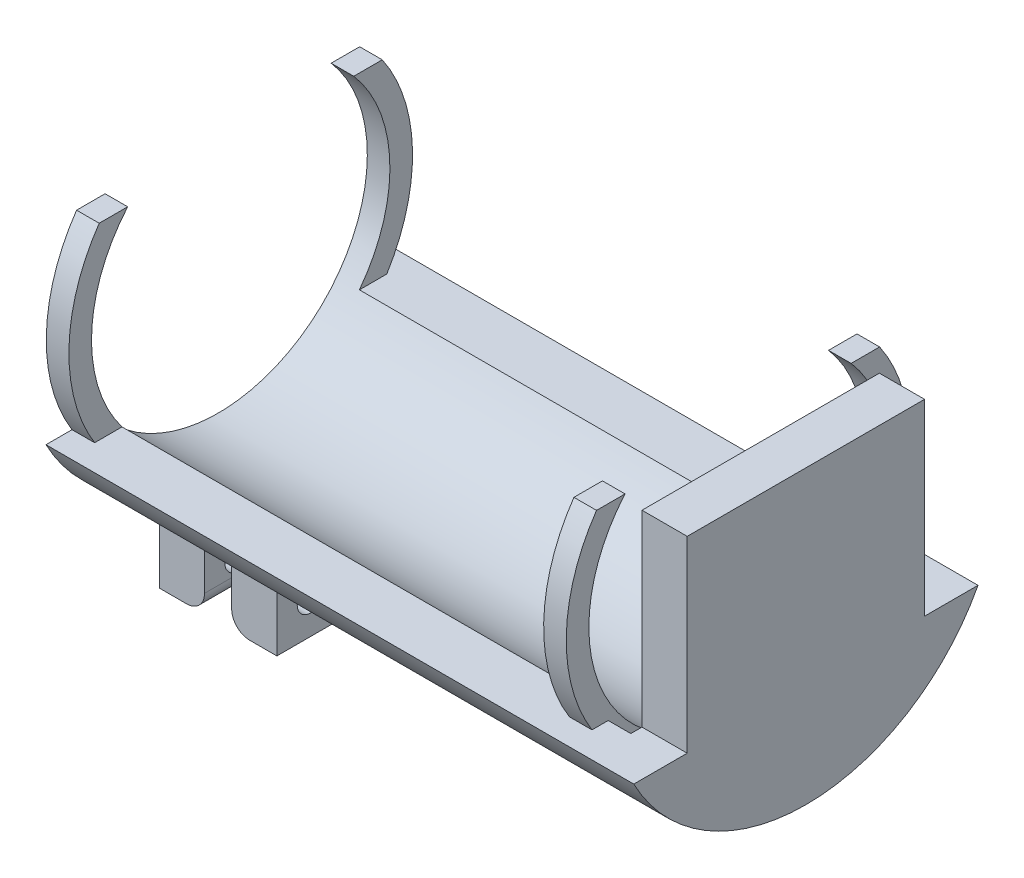
SolidWorks part; units mm, degrees
ref_plane "Front" through (0, 0, 0) normal (0, 0, 1) x (1, 0, 0)
ref_plane "Top" through (0, 0, 0) normal (0, 1, 0) x (1, 0, 0)
ref_plane "Right" through (0, 0, 0) normal (1, 0, 0) x (0, 0, -1)
sketch "Sketch1" plane through (0, 0, 0) normal (1, 0, 0) x (0, 0, -1)
  line L1 (-38.0657, -20) -> (-26.2488, -20)
  line L2 (26.2488, -20) -> (38.0657, -20)
  arc A0 (-26.2488, -20) -> (26.2488, -20) centre (0, 0) ccw
  arc A1 (-38.0657, -20) -> (38.0657, -20) centre (0, 0) ccw
  point P7 (-27.8818, -17.662)
  point P8 (27.8212, -17.6523)
  dimension "D1" = 66
  dimension "D2" = 10
  dimension "D3" = 20
extrude "Boss-Extrude1" add sketch "Sketch1" along normal mid plane 120
sketch "Sketch2" plane through (60, 0, 0) normal (1, 0, 0) x (0, 0, -1)
  line L0 (-31.305, 21.5407) -> (-25, 21.5407)
  line L1 (25, 21.5407) -> (31.305, 21.5407)
  arc A0 (-25, 21.5407) -> (25, 21.5407) centre (0, 0) ccw
  arc A1 (-31.305, 21.5407) -> (31.305, 21.5407) centre (0, 0) ccw
  dimension "D1" = 5
  dimension "D2" = 50
extrude "Boss-Extrude2" add sketch "Sketch2" against normal blind 5 from offset 5 offset against normal yes
sketch "Sketch3" plane through (60, 0, 0) normal (1, 0, 0) x (0, 0, -1)
  line L0 (-26.2488, -20) -> (-26.2488, 21.5407)
  line L1 (-26.2488, 21.5407) -> (26.2488, 21.5407)
  line L2 (26.2488, 21.5407) -> (26.2488, -20)
  line L3 (-25, 21.5407) -> (-31.305, 21.5407) construction
  line L4 (38.0657, -20) -> (26.2488, -20)
  line L7 (-26.2488, -20) -> (-38.0657, -20)
  line L8 (38.0657, -20) -> (26.2488, -20)
  line L11 (-26.2488, -20) -> (-38.0657, -20)
  arc A5 (-26.2488, -20) -> (26.2488, -20) centre (0, 0) ccw
  arc A7 (-38.0657, -20) -> (38.0657, -20) centre (0, 0) ccw
  arc A11 (-38.0657, -20) -> (38.0657, -20) centre (0, 0) ccw
  dimension "D1" = 0
extrude "Boss-Extrude3" add sketch "Sketch3" along normal blind 10
sketch "Sketch4" plane through (0, 0, 0) normal (0, 0, 1) x (1, 0, 0)
  line L0 (-48, -43) -> (-48, -54)
  line L1 (-60, -43) -> (70, -43) construction
  line L2 (-52, -58) -> (-58, -58)
  line L3 (-58, -58) -> (-58, -43)
  line L4 (-45, -43) -> (-45, -58) construction
  line L5 (-58, -43) -> (-48, -43)
  line L6 (-60, -20) -> (-60, -43) construction
  line L7 (-32, -43) -> (-42, -43)
  line L8 (-32, -58) -> (-32, -43)
  line L9 (-38, -58) -> (-32, -58)
  line L10 (-42, -43) -> (-42, -54)
  arc A0 (-38, -58) -> (-42, -54) centre (-38, -54) cw
  arc A1 (-48, -54) -> (-52, -58) centre (-52, -54) cw
  point P16 (-42, -58)
  point P19 (-48, -58)
  dimension "D5" = 4
  dimension "D1" = 15
  dimension "D2" = 3
  dimension "D3" = 10
  dimension "D4" = 15
extrude "Boss-Extrude4" add sketch "Sketch4" along normal mid plane 30 separate body
sketch "Sketch5" plane through (0, -43, 0) normal (0, 1, 0) x (1, 0, 0)
  line L0 (-32, 15) -> (-42, 15) construction
  line L1 (-42, 15) -> (-42, -15) construction
  line L2 (-42, -15) -> (-32, -15) construction
  line L3 (-32, -15) -> (-32, 15) construction
  line L4 (-48, 15) -> (-58, 15) construction
  line L5 (-58, 15) -> (-58, -15) construction
  line L6 (-58, -15) -> (-48, -15) construction
  line L7 (-48, -15) -> (-48, 15) construction
  line L8 (-32, 15) -> (-42, 15)
  line L9 (-42, 15) -> (-42, -15)
  line L10 (-42, -15) -> (-32, -15)
  line L11 (-32, -15) -> (-32, 15)
  line L12 (-48, 15) -> (-58, 15)
  line L13 (-58, 15) -> (-58, -15)
  line L14 (-58, -15) -> (-48, -15)
  line L15 (-48, -15) -> (-48, 15)
extrude "Boss-Extrude6" add sketch "Sketch5" along normal up to surface up to face at (5, -31.5, 0)
sketch "Sketch6" plane through (-58, 0, 0) normal (-1, 0, 0) x (0, 0, 1)
  line L0 (0, -43) -> (0, -58) construction
  line L1 (15, -58) -> (-15, -58) construction
  arc A0 (-15, -40.2989) -> (15, -40.2989) centre (0, 0) ccw construction
  circle A1 centre (-7.5, -50.5) radius 3
  circle A2 centre (7.5, -50.5) radius 3
  point P9 (0, 0)
  point P10 (0, -50.5)
  dimension "D2" = 6
  dimension "D1" = 7.5
extrude "Cut-Extrude1" cut sketch "Sketch6" against normal up to surface (26 mm away) up to face at (-32, -49.8247, 0)
sketch "Sketch7" plane through (60, 0, 0) normal (-1, 0, 0) x (0, 0, 1)
  circle A0 centre (0, 0) radius 35
  dimension "D1" = 70
extrude "Cut-Extrude2" cut sketch "Sketch7" along normal up to surface (5 mm away) up to face at (55, 0.8631, 32.1016)
pattern_linear "LPattern1" count 2 spacing 110 along (-1, 0, 0) of "Boss-Extrude2"
